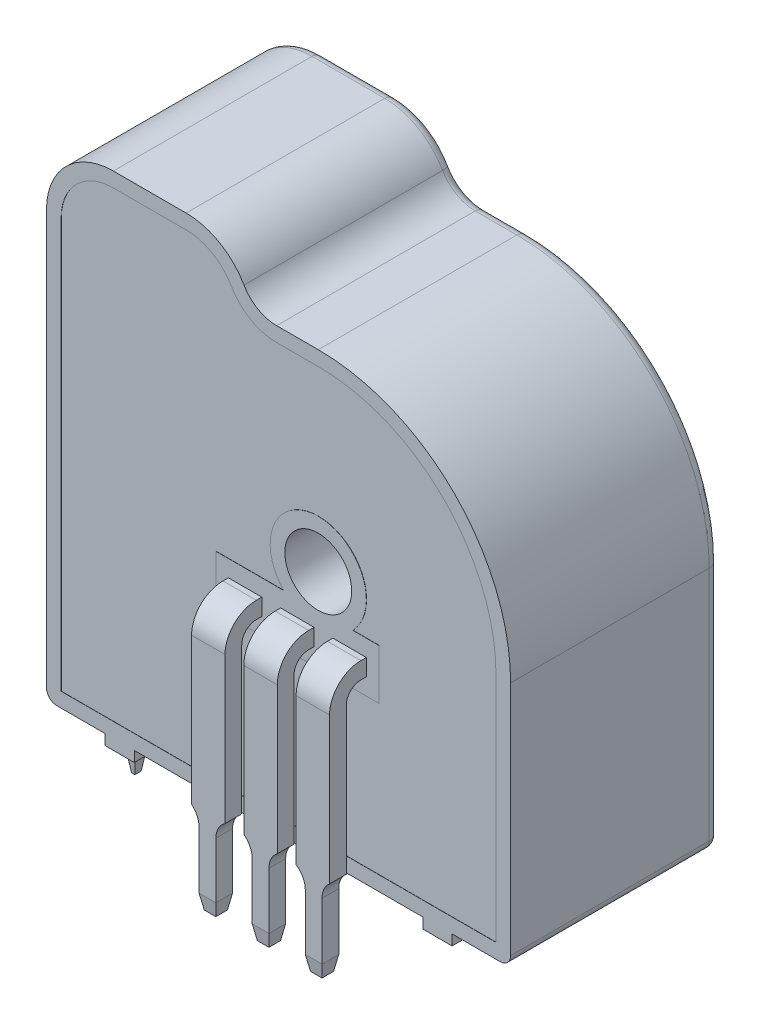
SolidWorks part; units mm, degrees
ref_plane "Front Plane" through (0, 0, 0) normal (0, 0, 1) x (1, 0, 0)
ref_plane "Top Plane" through (0, 0, 0) normal (0, 1, 0) x (1, 0, 0)
ref_plane "Right Plane" through (0, 0, 0) normal (1, 0, 0) x (0, 0, -1)
sketch "Sketch1" plane through (0, 0, 0) normal (0, 0, 1) x (1, 0, 0)
  line L0 (0, 0) -> (22.2, 0)
  line L1 (22.2, 0) -> (22.2, 21)
  line L2 (22.2, 21) -> (9.8, 21)
  line L3 (9.8, 21) -> (9.8, 23.5)
  line L4 (0, 0) -> (0, 23.5)
  line L5 (0, 23.5) -> (9.8, 23.5)
  circle A0 centre (13, 11.8) radius 1.6
  point P0 (0, 0)
  dimension "D5" = 9.2
  dimension "D1" = 12.4
  dimension "D2" = 22.2
  dimension "D3" = 21
  dimension "D4" = 23.5
  dimension "D6" = 11.8
extrude "Boss-Extrude1" add sketch "Sketch1" along normal blind 10
fillet "Fillet1" radius 9.2 1 edges at (22.2, 21, 5)
fillet "Fillet2" radius 3.2 2 edges at (9.8, 23.5, 5) (0, 23.5, 5)
fillet "Fillet3" radius 1.8 1 edges at (9.8, 21, 5)
fillet "Fillet4" radius 0.5 11 edges at (0, 10.15, 0) (22.2, 5.9, 0) (19.5054, 18.3054, 0) (12.0038, 21, 0) (8.2775, 23.0713, 0) (4.9388, 23.5, 0) (11.1, 0, 0) (22.2, 0, 5) (0, 0, 5) (0.9373, 22.5627, 0) (10.1076, 21.2412, 0)
sketch "Sketch4" plane through (0, 0, 10) normal (0, 0, 1) x (1, 0, 0)
  line L0 (0.5, 0) -> (21.7, 0) construction
  line L1 (8.1, 7.8) -> (15.9, 7.8)
  line L2 (8.1, 7.8) -> (8.1, 10.2)
  line L3 (8.1, 10.2) -> (11.3477, 10.2)
  line L4 (15.9, 7.8) -> (15.9, 10.2)
  line L5 (0, 20.3) -> (0, 0.5) construction
  line L8 (14.6523, 10.2) -> (15.9, 10.2)
  line L10 (0.7, 0.7) -> (21.5, 0.7)
  line L11 (21.5, 0.7) -> (21.5, 11.8)
  line L12 (13, 20.3) -> (11.0076, 20.3)
  line L13 (6.6775, 22.8) -> (3.2, 22.8)
  line L14 (0.7, 20.3) -> (0.7, 0.7)
  line L15 (0.7, 0.7) -> (21.5, 0.7)
  line L16 (21.5, 0.7) -> (21.5, 11.8)
  line L17 (13, 20.3) -> (11.0076, 20.3)
  line L18 (6.6775, 22.8) -> (3.2, 22.8)
  line L19 (0.7, 20.3) -> (0.7, 0.7)
  circle A8 centre (13, 11.8) radius 2.3
  arc A9 (14.6523, 10.2) -> (11.3477, 10.2) centre (13, 11.8) ccw
  arc A12 (21.5, 11.8) -> (13, 20.3) centre (13, 11.8) ccw
  arc A13 (8.8426, 21.55) -> (11.0076, 20.3) centre (11.0076, 22.8) ccw
  arc A14 (8.8426, 21.55) -> (6.6775, 22.8) centre (6.6775, 20.3) ccw
  arc A15 (3.2, 22.8) -> (0.7, 20.3) centre (3.2, 20.3) ccw
  arc A16 (21.5, 11.8) -> (13, 20.3) centre (13, 11.8) ccw
  arc A17 (8.8426, 21.55) -> (11.0076, 20.3) centre (11.0076, 22.8) ccw
  arc A18 (8.8426, 21.55) -> (6.6775, 22.8) centre (6.6775, 20.3) ccw
  arc A19 (3.2, 22.8) -> (0.7, 20.3) centre (3.2, 20.3) ccw
  dimension "D3" = 2.4
  dimension "D4" = 7.8
  dimension "D5" = 7.8
  dimension "D6" = 8.1
  dimension "D1" = 0.7
  dimension "D2" = 0.7
extrude "Cut-Extrude1" cut sketch "Sketch4" against normal blind 0.01
sketch "Sketch8" plane through (0, 0, 10) normal (0, 0, 1) x (1, 0, 0)
  line L0 (8.1, 9) -> (8.7, 9) construction
  line L1 (8.7, 9.4) -> (10.3, 9.4)
  line L2 (8.7, 9.4) -> (8.7, 8.6)
  line L3 (8.7, 8.6) -> (10.3, 8.6)
  line L4 (10.3, 9.4) -> (10.3, 8.6)
  line L5 (11.2, 9.4) -> (12.8, 9.4)
  line L6 (11.2, 9.4) -> (11.2, 8.6)
  line L7 (11.2, 8.6) -> (12.8, 8.6)
  line L8 (12.8, 9.4) -> (12.8, 8.6)
  line L9 (13.7, 9.4) -> (15.3, 9.4)
  line L10 (13.7, 9.4) -> (13.7, 8.6)
  line L11 (13.7, 8.6) -> (15.3, 8.6)
  line L12 (15.3, 9.4) -> (15.3, 8.6)
  line L13 (8.1, 10.2) -> (8.1, 7.8) construction
  line L14 (15.3, 9) -> (15.9, 9) construction
  line L15 (15.9, 7.8) -> (15.9, 10.2) construction
  line L16 (10.3, 9) -> (11.2, 9) construction
  line L17 (12.8, 9) -> (13.7, 9) construction
  dimension "D1" = 0.9
  dimension "D2" = 1.6
  dimension "D3" = 0.8
  dimension "D4" = 0.6
extrude "Boss-Extrude2" add sketch "Sketch8" along normal blind 0.26 and the other way blind 10.24
sketch "Sketch9" plane through (0, 0, 10.26) normal (0, 0, 1) x (1, 0, 0)
  line L1 (12.8, 8.6) -> (12.8, 9.4) construction
  line L2 (11.2, 8.6) -> (12.8, 8.6)
  line L3 (11.2, 8.6) -> (11.2, 9.4)
  line L6 (10.3, 8.6) -> (10.3, 9.4) construction
  line L7 (13.7, 9.4) -> (15.3, 9.4)
  line L8 (13.7, 9.4) -> (13.7, 8.6)
  line L9 (13.7, 8.6) -> (15.3, 8.6)
  line L10 (15.3, 9.4) -> (15.3, 8.6)
  line L11 (10.3, 8.6) -> (8.7, 8.6)
  line L12 (10.3, 8.6) -> (10.3, 9.4)
  line L13 (10.3, 9.4) -> (8.7, 9.4)
  line L14 (8.7, 8.6) -> (8.7, 9.4)
  line L15 (8.7, 9.4) -> (8.7, 8.6) construction
  line L16 (10.3, 9.4) -> (8.7, 9.4) construction
  line L17 (11.2, 9.4) -> (12.8, 9.4)
  line L18 (12.8, 8.6) -> (12.8, 9.4)
  line L19 (11.2, 8.6) -> (12.8, 9.4) construction
  line L20 (11.2, 9.4) -> (12.8, 8.6) construction
  line L21 (11.2, 9.4) -> (11.2, 8.6) construction
  line L22 (12.8, 9.4) -> (11.2, 9.4) construction
  line L23 (11.2, 8.6) -> (12.8, 8.6) construction
  point P0 (12, 9)
ref_plane "Plane1" through (12, 0, 0) normal (1, 0, 0) x (0, 0, -1)
sketch "Sketch11" plane through (12, 0, 0) normal (1, 0, 0) x (0, 0, -1)
  arc A0 (-10.26, 9) -> (-11.36, 7.9) centre (-10.26, 7.9) ccw
sweep "Sweep4" add profiles "Sketch9" path "Sketch11"
sketch "Sketch12" plane through (0, 7.9, 0) normal (0, -1, 0) x (1, 0, 0)
  line L1 (11.2, 10.96) -> (12.8, 10.96)
  line L2 (11.2, 10.96) -> (11.2, 11.76)
  line L3 (11.2, 11.76) -> (12.8, 11.76)
  line L4 (12.8, 10.96) -> (12.8, 11.76)
  line L5 (13.7, 11.76) -> (15.3, 11.76)
  line L6 (13.7, 11.76) -> (13.7, 10.96)
  line L7 (13.7, 10.96) -> (15.3, 10.96)
  line L8 (15.3, 11.76) -> (15.3, 10.96)
  line L9 (10.3, 11.76) -> (8.7, 11.76)
  line L10 (10.3, 11.76) -> (10.3, 10.96)
  line L11 (10.3, 10.96) -> (8.7, 10.96)
  line L12 (8.7, 11.76) -> (8.7, 10.96)
extrude "Boss-Extrude3" add sketch "Sketch12" along normal blind 7
sketch "Sketch13" plane through (0, 0, -0.24) normal (0, 0, -1) x (-1, 0, 0)
  line L0 (-8.7, 8.6) -> (-10.3, 8.6) construction
  line L1 (-13.7, 9.4) -> (-15.3, 9.4)
  line L2 (-13.7, 9.4) -> (-13.7, 8.6)
  line L3 (-13.7, 8.6) -> (-15.3, 8.6)
  line L4 (-15.3, 9.4) -> (-15.3, 8.6)
  line L5 (-8.7, 8.6) -> (-10.3, 8.6)
  line L6 (-8.7, 8.6) -> (-8.7, 9.4)
  line L7 (-8.7, 9.4) -> (-10.3, 9.4)
  line L8 (-10.3, 8.6) -> (-10.3, 9.4)
  line L9 (-8.7, 9.4) -> (-8.7, 8.6) construction
  line L10 (-11.2, 8.6) -> (-12.8, 8.6) construction
  line L11 (-12.8, 9.4) -> (-11.2, 9.4)
  line L12 (-12.8, 9.4) -> (-12.8, 8.6)
  line L13 (-12.8, 8.6) -> (-11.2, 8.6)
  line L14 (-11.2, 9.4) -> (-11.2, 8.6)
  line L15 (-12.8, 9.4) -> (-11.2, 8.6) construction
  line L16 (-12.8, 8.6) -> (-11.2, 9.4) construction
  line L17 (-11.2, 8.6) -> (-11.2, 9.4) construction
  line L18 (-12.8, 8.6) -> (-12.8, 9.4) construction
  line L19 (-12, 6.6) -> (-12, -6.6) construction
  point P15 (-12, 9)
sketch "Sketch14" plane through (12, 0, 0) normal (1, 0, 0) x (0, 0, -1)
  arc A0 (0.24, 9) -> (1.34, 7.9) centre (0.24, 7.9) cw
sweep "Sweep5" add profiles "Sketch13" path "Sketch14"
sketch "Sketch16" plane through (0, 7.9, 0) normal (0, -1, 0) x (1, 0, 0)
  line L1 (11.2, -0.94) -> (12.8, -0.94)
  line L2 (11.2, -0.94) -> (11.2, -1.74)
  line L3 (11.2, -1.74) -> (12.8, -1.74)
  line L4 (12.8, -0.94) -> (12.8, -1.74)
  line L5 (13.7, -0.94) -> (15.3, -0.94)
  line L6 (13.7, -0.94) -> (13.7, -1.74)
  line L7 (13.7, -1.74) -> (15.3, -1.74)
  line L8 (15.3, -0.94) -> (15.3, -1.74)
  line L9 (8.7, -0.94) -> (10.3, -0.94)
  line L10 (8.7, -0.94) -> (8.7, -1.74)
  line L11 (8.7, -1.74) -> (10.3, -1.74)
  line L12 (10.3, -0.94) -> (10.3, -1.74)
extrude "Boss-Extrude5" add sketch "Sketch16" along normal blind 7
sketch "Sketch17" plane through (0, 0.9, 0) normal (0, -1, 0) x (1, 0, 0)
  line L0 (10.3, -0.94) -> (8.7, -0.94) construction
  line L1 (11.6, -0.94) -> (12.4, -0.94)
  line L2 (11.6, -0.94) -> (11.6, -1.74)
  line L3 (11.6, -1.74) -> (12.4, -1.74)
  line L4 (12.4, -0.94) -> (12.4, -1.74)
  line L5 (11.6, -0.94) -> (12.4, -1.74) construction
  line L6 (11.6, -1.74) -> (12.4, -0.94) construction
  line L7 (14.94, -0.94) -> (14.14, -0.94)
  line L8 (14.94, -0.94) -> (14.94, -1.74)
  line L9 (14.94, -1.74) -> (14.14, -1.74)
  line L10 (14.14, -0.94) -> (14.14, -1.74)
  line L11 (14.94, -0.94) -> (14.14, -1.74) construction
  line L12 (14.94, -1.74) -> (14.14, -0.94) construction
  line L13 (9.06, -0.94) -> (9.86, -0.94)
  line L14 (9.06, -0.94) -> (9.06, -1.74)
  line L15 (9.06, -1.74) -> (9.86, -1.74)
  line L16 (9.86, -0.94) -> (9.86, -1.74)
  line L17 (9.06, -0.94) -> (9.86, -1.74) construction
  line L18 (9.06, -1.74) -> (9.86, -0.94) construction
  line L19 (14.94, 11.76) -> (14.14, 11.76)
  line L20 (14.94, 11.76) -> (14.94, 10.96)
  line L21 (14.94, 10.96) -> (14.14, 10.96)
  line L22 (14.14, 11.76) -> (14.14, 10.96)
  line L23 (14.94, 11.76) -> (14.14, 10.96) construction
  line L24 (14.94, 10.96) -> (14.14, 11.76) construction
  line L25 (11.6, 11.76) -> (12.4, 11.76)
  line L26 (11.6, 11.76) -> (11.6, 10.96)
  line L27 (11.6, 10.96) -> (12.4, 10.96)
  line L28 (12.4, 11.76) -> (12.4, 10.96)
  line L29 (11.6, 11.76) -> (12.4, 10.96) construction
  line L30 (11.6, 10.96) -> (12.4, 11.76) construction
  line L31 (9.06, 11.76) -> (9.86, 11.76)
  line L32 (9.06, 11.76) -> (9.06, 10.96)
  line L33 (9.06, 10.96) -> (9.86, 10.96)
  line L34 (9.86, 11.76) -> (9.86, 10.96)
  line L35 (9.06, 11.76) -> (9.86, 10.96) construction
  line L36 (9.06, 10.96) -> (9.86, 11.76) construction
  line L37 (12.8, -0.94) -> (11.2, -0.94) construction
  line L38 (15.3, -0.94) -> (13.7, -0.94) construction
  line L39 (13.7, -1.74) -> (15.3, -1.74) construction
  line L40 (13.7, 10.96) -> (15.3, 10.96) construction
  line L41 (11.2, 10.96) -> (12.8, 10.96) construction
  line L42 (8.7, 10.96) -> (10.3, 10.96) construction
  line L43 (12, -6.6) -> (12, 6.6) construction
  point P0 (12, -1.34)
  point P5 (14.54, -1.34)
  point P10 (9.46, -1.34)
  point P15 (14.54, 11.36)
  point P20 (12, 11.36)
  point P25 (9.46, 11.36)
  dimension "D1" = 0.8
  dimension "D2" = 2.54
  dimension "D3" = 2.54
  dimension "D4" = 2.54
  dimension "D5" = 2.54
extrude "Boss-Extrude6" add sketch "Sketch17" along normal blind 3.5
sketch "Sketch18" plane through (0, -2.6, 0) normal (0, -1, 0) x (1, 0, 0)
  line L1 (12.4, 11.76) -> (11.6, 11.76)
  line L2 (12.4, 11.76) -> (12.4, 10.96)
  line L3 (12.4, 10.96) -> (11.6, 10.96)
  line L4 (11.6, 11.76) -> (11.6, 10.96)
  line L5 (14.14, 10.96) -> (14.94, 10.96)
  line L6 (14.14, 10.96) -> (14.14, 11.76)
  line L7 (14.14, 11.76) -> (14.94, 11.76)
  line L8 (14.94, 10.96) -> (14.94, 11.76)
  line L9 (9.06, 10.96) -> (9.86, 10.96)
  line L10 (9.06, 10.96) -> (9.06, 11.76)
  line L11 (9.06, 11.76) -> (9.86, 11.76)
  line L12 (9.86, 10.96) -> (9.86, 11.76)
  line L13 (14.14, -1.74) -> (14.94, -1.74)
  line L14 (14.14, -1.74) -> (14.14, -0.94)
  line L15 (14.14, -0.94) -> (14.94, -0.94)
  line L16 (14.94, -1.74) -> (14.94, -0.94)
  line L17 (12.4, -0.94) -> (11.6, -0.94)
  line L18 (12.4, -0.94) -> (12.4, -1.74)
  line L19 (12.4, -1.74) -> (11.6, -1.74)
  line L20 (11.6, -0.94) -> (11.6, -1.74)
  line L21 (9.86, -0.94) -> (9.06, -0.94)
  line L22 (9.86, -0.94) -> (9.86, -1.74)
  line L23 (9.86, -1.74) -> (9.06, -1.74)
  line L24 (9.06, -0.94) -> (9.06, -1.74)
extrude "Boss-Extrude7" add sketch "Sketch18" along normal blind 0.7 draft 10
fillet "Fillet5" radius 1 12 edges
sketch "Sketch22" plane through (0, 0, 0) normal (0, -1, 0) x (1, 0, 0)
  line L0 (0.5, 0.5) -> (21.7, 0.5) construction
  line L1 (2.8, 0.5) -> (4.2, 0.5)
  line L2 (2.8, 0.5) -> (2.8, 10)
  line L3 (2.8, 10) -> (4.2, 10)
  line L4 (4.2, 0.5) -> (4.2, 10)
  line L5 (0.5, 10) -> (21.7, 10) construction
  line L6 (0, 0.5) -> (0, 10) construction
  line L7 (18, 0.5) -> (19.4, 0.5)
  line L8 (18, 0.5) -> (18, 10)
  line L9 (18, 10) -> (19.4, 10)
  line L10 (19.4, 0.5) -> (19.4, 10)
  dimension "D1" = 1.4
  dimension "D2" = 13.8
  dimension "D3" = 2.8
extrude "Boss-Extrude8" add sketch "Sketch22" along normal blind 0.5
sketch "Sketch23" plane through (0, 0, 0) normal (0, -1, 0) x (1, 0, 0)
  line L0 (1.84, 11.0702) -> (1.84, -1.8281) construction
  line L1 (12, -7.4735) -> (12, 7.4735) construction
  line L2 (0.5, 10) -> (2.8, 10) construction
  line L3 (2.015, 5.25) -> (1.665, 5.25)
  line L4 (2.015, 5.25) -> (2.015, 4.75)
  line L5 (2.015, 4.75) -> (1.665, 4.75)
  line L6 (1.665, 5.25) -> (1.665, 4.75)
  line L7 (2.015, 5.25) -> (1.665, 4.75) construction
  line L8 (2.015, 4.75) -> (1.665, 5.25) construction
  line L9 (1.665, 7.29) -> (2.015, 7.29)
  line L10 (1.665, 7.29) -> (1.665, 7.79)
  line L11 (1.665, 7.79) -> (2.015, 7.79)
  line L12 (2.015, 7.29) -> (2.015, 7.79)
  line L13 (1.665, 7.29) -> (2.015, 7.79) construction
  line L14 (1.665, 7.79) -> (2.015, 7.29) construction
  line L15 (1.665, 2.71) -> (2.015, 2.71)
  line L16 (1.665, 2.71) -> (1.665, 2.21)
  line L17 (1.665, 2.21) -> (2.015, 2.21)
  line L18 (2.015, 2.71) -> (2.015, 2.21)
  line L19 (1.665, 2.71) -> (2.015, 2.21) construction
  line L20 (1.665, 2.21) -> (2.015, 2.71) construction
  point P4 (1.84, 5)
  point P9 (1.84, 7.54)
  point P14 (1.84, 2.46)
  dimension "D1" = 10.16
  dimension "D2" = 0.35
  dimension "D3" = 0.5
  dimension "D4" = 2.04
  dimension "D5" = 2.04
  dimension "D6" = 2.21
extrude "Boss-Extrude9" add sketch "Sketch23" along normal up to vertex (2.6 mm away) up to point (9.06, -2.6, 11.76)
sketch "Sketch24" plane through (0, -2.6, 0) normal (0, -1, 0) x (1, 0, 0)
  line L0 (2.015, 4.75) -> (2.015, 5.25) construction
  line L1 (1.665, 5.25) -> (2.015, 5.25)
  line L2 (1.665, 5.25) -> (1.665, 4.75)
  line L3 (1.665, 4.75) -> (2.015, 4.75)
  line L4 (2.015, 5.25) -> (2.015, 4.75)
  line L5 (1.665, 4.75) -> (2.015, 4.75) construction
  line L7 (1.665, 7.79) -> (2.015, 7.79)
  line L8 (1.665, 7.79) -> (1.665, 7.29)
  line L9 (1.665, 7.29) -> (2.015, 7.29)
  line L10 (2.015, 7.79) -> (2.015, 7.29)
  line L11 (1.665, 2.71) -> (2.015, 2.71)
  line L12 (1.665, 2.71) -> (1.665, 2.21)
  line L13 (1.665, 2.21) -> (2.015, 2.21)
  line L14 (2.015, 2.71) -> (2.015, 2.21)
extrude "Boss-Extrude10" add sketch "Sketch24" along normal up to vertex (0.7 mm away) draft 8 up to point (9.1834, -3.3, 11.6366)
sketch "Sketch25" plane through (0, 0, 0) normal (-1, 0, 0) x (0, 0, 1)
  line L0 (2.0347, 7.6955) -> (6.6742, 7.6955)
  line L1 (6.6742, 7.6955) -> (6.6742, 8.6557)
  line L2 (6.6742, 8.6557) -> (8.5848, 6.7451)
  line L3 (8.5848, 6.7451) -> (6.6742, 4.8344)
  line L4 (6.6742, 4.8344) -> (6.6742, 5.7947)
  line L5 (6.6742, 5.7947) -> (2.0347, 5.7947)
  line L6 (2.0347, 5.7947) -> (2.0347, 6.7451)
  line L7 (0.9742, 6.7451) -> (9.0699, 6.7451) construction
  line L8 (2.0347, 7.6955) -> (2.0347, 6.7451)
  line L9 (3.22, 0.7267) -> (3.22, 3.8769) construction
  line L10 (5.76, 0.8776) -> (5.76, 3.8769) construction
  line L11 (8.3, 0.8776) -> (8.3, 3.8769) construction
  line L12 (10, 20.3) -> (10, 0.5) construction
  text T0 "+" font "Century Gothic" height 2
  text T1 "0" font "Century Gothic" height 1.6
  text T2 "Out" font "Calibri" height 1.6
  dimension "D1" = 2.54
  dimension "D2" = 2.54
  dimension "D3" = 1.7
extrude "Boss-Extrude11" add sketch "Sketch25" along normal blind 0.05
sketch "Sketch27" plane through (0, 0, 0) normal (0, 0, -1) x (-1, 0, 0)
  line L2 (-10.4584, 13.5462) -> (-10.5964, 12.707)
  line L3 (-10.5964, 12.707) -> (-4.0516, 12.707)
  line L4 (-4.0516, 12.707) -> (-3.9136, 13.5462)
  line L5 (-3.9136, 13.5462) -> (-10.4584, 13.5462)
  line L6 (-10.5964, 12.5614) -> (-10.6565, 12.1958)
  line L7 (-10.6565, 12.1958) -> (-4.1322, 12.1958)
  line L8 (-4.1322, 12.1958) -> (-4.0721, 12.5614)
  line L9 (-4.0721, 12.5614) -> (-10.5964, 12.5614)
  line L10 (-5.3864, 8.8923) -> (-5.3864, 2.605) construction
  line L11 (-1.8619, 8.8923) -> (-1.8619, 2.4636) construction
  line L12 (-2.1922, 6.1385) -> (-3.264, 6.1385)
  line L13 (-2.1922, 6.1385) -> (-2.1922, 5.5171)
  line L14 (-3.264, 5.5171) -> (-2.1922, 5.5171)
  line L16 (-1.8619, 7.8639) -> (-1.8619, 7.2639)
  line L17 (-1.8619, 4.3917) -> (-1.8619, 3.7917)
  line L18 (-5.3864, 7.8639) -> (-5.3864, 7.2639)
  line L19 (-5.3864, 4.3917) -> (-5.3864, 3.7917)
  arc A0 (-5.3864, 7.8639) -> (-5.3864, 3.7917) centre (-5.3864, 5.8278) ccw
  arc A1 (-1.8619, 7.8639) -> (-1.8619, 3.7917) centre (-1.8619, 5.8278) ccw
  arc A2 (-5.3864, 7.2639) -> (-5.3864, 4.3917) centre (-5.3864, 5.8278) ccw
  arc A3 (-1.8619, 7.2639) -> (-3.264, 6.1385) centre (-1.8619, 5.8278) ccw
  arc A4 (-3.264, 5.5171) -> (-1.8619, 4.3917) centre (-1.8619, 5.8278) ccw
  circle A5 centre (-5.3864, 5.8278) radius 1.4361 construction
  circle A6 centre (-5.3864, 5.8278) radius 2.0361 construction
  point P22 (-3.4393, 6.4231)
  point P23 (-3.9503, 5.8278)
  dimension "D1" = 0.6
sketch "Sketch28" plane through (0, 0, 0) normal (0, 0, -1) x (-1, 0, 0)
  line L0 (-10.5964, 13.8281) -> (-2.4676, 13.8281) construction
  text T0 "LEM" font "Arial Narrow" height 2.9
  point P11 (-5.3864, 5.8278)
  point P21 (-5.3864, 5.8278)
  point P22 (-3.4393, 6.4231)
  point P23 (-3.9503, 5.8278)
extrude "Cut-Extrude2" cut sketch "Sketch27" against normal blind 0.1
extrude "Cut-Extrude3" cut sketch "Sketch28" against normal blind 0.1
